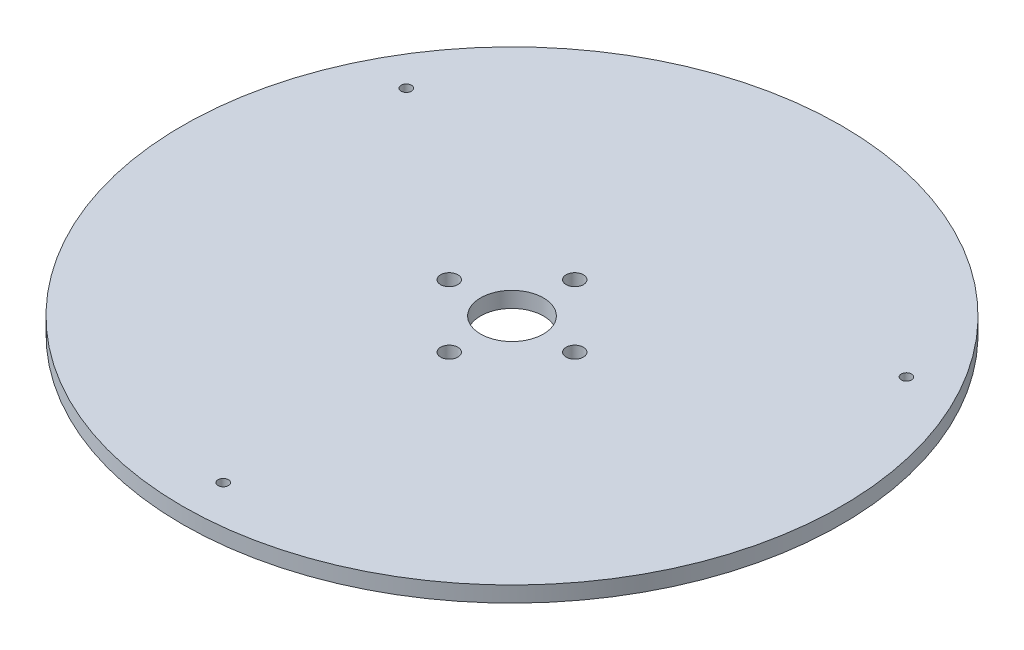
SolidWorks part; units mm, degrees
material "AISI 1020"
ref_plane "Plan de face" through (0, 0, 0) normal (0, 0, 1) x (1, 0, 0)
ref_plane "Plan de dessus" through (0, 0, 0) normal (0, 1, 0) x (1, 0, 0)
ref_plane "Plan de droite" through (0, 0, 0) normal (1, 0, 0) x (0, 0, -1)
sketch "Esquisse1" plane through (0, 0, 0) normal (0, 1, 0) x (1, 0, 0)
  circle A0 centre (0, 0) radius 105
  circle A1 centre (0, 0) radius 10
  dimension "D1" = 210
  dimension "D2" = 20
extrude "Boss.-Extru.1" add sketch "Esquisse1" along normal blind 5
hole_wizard "Trou pour taraudage pour trou taraudé M41" positions "Esquisse4" profile "Esquisse5" hole size "M4" standard "ISO" end condition through all
sketch "Esquisse4" plane through (0, 5, 0) normal (0, 1, 0) x (1, 0, 0)
  line L0 (0, 129.6397) -> (0, -144.8986) construction
  circle A0 centre (0, 0) radius 92 construction
  point P0 (0, -92)
  dimension "D1" = 184
sketch "Esquisse5" plane through (0, 5, 92) normal (1, 0, 0) x (0, 0, 1)
  line L0 (0, 0) -> (0, 5)
  line L1 (0, 5) -> (1.65, 5)
  line L2 (1.65, 5) -> (1.65, 0)
  line L5 (1.65, 0) -> (0, 0)
  line L11 (0, -6.35) -> (0, 107.95) construction
  dimension "Diamètre du perçage jusqu'au prochain" = 3.3
  dimension "Profondeur du perçage jusqu'au prochain" = 5
ref_axis "Axe1" through (0, 5, 0) along (0, -1, 0)
pattern_circular "Répétition circulaire1" count 3 over 360 about axis through (0, 5, 0) along (0, -1, 0) of "Trou pour taraudage pour trou taraudé M41"
hole_wizard "Dégagement M51" positions "Esquisse6" profile "Esquisse7" hole size "M5" standard "ISO" end condition through all
sketch "Esquisse6" plane through (0, 5, 0) normal (0, 1, 0) x (1, 0, 0)
  line L0 (0, -72.2108) -> (0, 43.0448) construction
  circle A0 centre (0, 0) radius 20 construction
  point P0 (0, -20)
  dimension "D1" = 40
sketch "Esquisse7" plane through (0, 5, 20) normal (1, 0, 0) x (0, 0, 1)
  line L0 (0, 0) -> (0, 5)
  line L1 (0, 5) -> (2.75, 5)
  line L2 (2.75, 5) -> (2.75, 0)
  line L5 (2.75, 0) -> (0, 0)
  line L11 (0, -6.35) -> (0, 107.95) construction
  dimension "Diamètre du perçage jusqu'au prochain" = 5.5
  dimension "Profondeur du perçage jusqu'au prochain" = 5
pattern_circular "Répétition circulaire2" count 4 over 360 about axis through (0, 5, 0) along (0, -1, 0) of "Dégagement M51"
